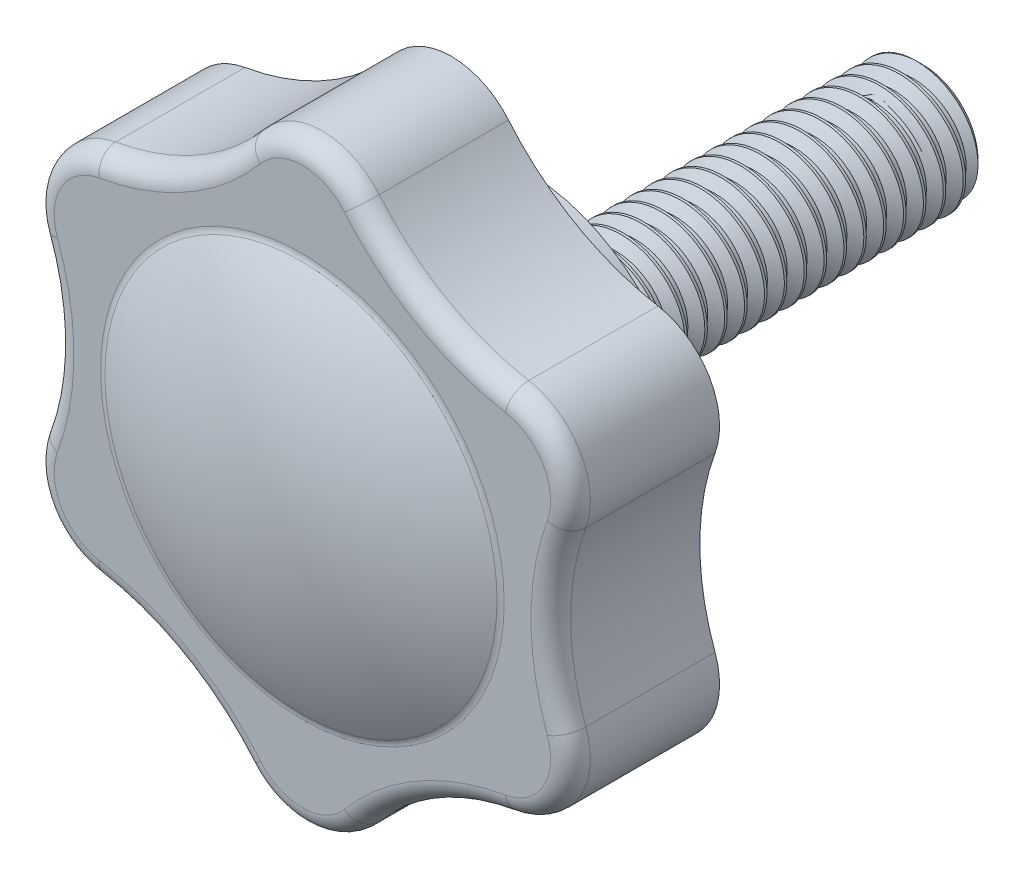
SolidWorks part; units mm, degrees
ref_plane "Front Plane" through (0, 0, 0) normal (0, 0, 1) x (1, 0, 0)
ref_plane "Top Plane" through (0, 0, 0) normal (0, 1, 0) x (1, 0, 0)
ref_plane "Right Plane" through (0, 0, 0) normal (1, 0, 0) x (0, 0, -1)
sketch "Sketch1" plane through (0, 0, 0) normal (0, 0, 1) x (1, 0, 0)
  circle A0 centre (0, 0) radius 6.5
  dimension "D1" = 13
extrude "Boss-Extrude1" add sketch "Sketch1" along normal blind 3
sketch "Sketch2" plane through (0, 0, 3) normal (0, 0, 1) x (1, 0, 0)
  line L0 (0, 0) -> (0, 17.4391) construction
  line L2 (14.0075, 8.0872) -> (0, 0) construction
  circle A0 centre (0, 0) radius 12 construction
  circle A1 centre (0, 0) radius 10 construction
  arc A2 (2.2988, 10.9276) -> (0, 12) centre (0, 9) ccw
  arc A3 (10.3923, 6) -> (8.3142, 7.4546) centre (7.7942, 4.5) ccw
  arc A4 (2.2988, 10.9276) -> (8.3142, 7.4546) centre (10.0727, 17.4464) ccw
  arc A5 (10.613, 3.473) -> (10.3923, 6) centre (7.7942, 4.5) ccw
  arc A6 (10.613, 3.473) -> (10.613, -3.473) centre (20.1453, 0) ccw
  arc A7 (10.3923, -6) -> (10.613, -3.473) centre (7.7942, -4.5) ccw
  arc A8 (8.3142, -7.4546) -> (10.3923, -6) centre (7.7942, -4.5) ccw
  arc A9 (8.3142, -7.4546) -> (2.2988, -10.9276) centre (10.0727, -17.4464) ccw
  arc A10 (0, -12) -> (2.2988, -10.9276) centre (0, -9) ccw
  arc A11 (-2.2988, -10.9276) -> (0, -12) centre (0, -9) ccw
  arc A12 (-2.2988, -10.9276) -> (-8.3142, -7.4546) centre (-10.0727, -17.4464) ccw
  arc A13 (-10.3923, -6) -> (-8.3142, -7.4546) centre (-7.7942, -4.5) ccw
  arc A14 (-10.613, -3.473) -> (-10.3923, -6) centre (-7.7942, -4.5) ccw
  arc A15 (-10.613, -3.473) -> (-10.613, 3.473) centre (-20.1453, 0) ccw
  arc A16 (-10.3923, 6) -> (-10.613, 3.473) centre (-7.7942, 4.5) ccw
  arc A17 (-8.3142, 7.4546) -> (-10.3923, 6) centre (-7.7942, 4.5) ccw
  arc A18 (-8.3142, 7.4546) -> (-2.2988, 10.9276) centre (-10.0727, 17.4464) ccw
  arc A19 (0, 12) -> (-2.2988, 10.9276) centre (0, 9) ccw
  dimension "D1" = 24
  dimension "D3" = 20
  dimension "D4" = 6
  dimension "D2" = 60
  dimension "D5" = 6
extrude "Boss-Extrude2" add sketch "Sketch2" along normal blind 6
sketch "Sketch4" plane through (0, 0, 0) normal (0, 1, 0) x (1, 0, 0)
  line L1 (6.5, 0) -> (-6.5, 0) construction
  line L2 (-8, -9) -> (8, -9) construction
  line L3 (-2.2988, -9) -> (2.2988, -9) construction
  line L4 (0, 0) -> (0, 4.0899) construction
  line L5 (-8, -9) -> (8, -9)
  line L6 (0, -11) -> (0, -9)
  arc A0 (-8, -9) -> (0, -11) centre (0, 6) ccw
  dimension "D1" = 11
  dimension "D2" = 16
revolve "Revolve3" add sketch "Sketch4" angle 360 about L4 region at (-3.025, 0, 9.8042)
sketch "Sketch6" plane through (0, 0, 3) normal (0, 0, -1) x (-1, 0, 0)
  circle A0 centre (0, 0) radius 8.5
  circle M2 centre (0, 0) radius 6.5
  dimension "D1" = 17
extrude "Cut-Extrude1" cut sketch "Sketch6" against normal blind 4 contours A0 M2 region at (8.2596, 0, 3)
fillet "Fillet1" radius 0.8 12 edges at (0, 12, 9) (5, 8.6603, 9) (10.3923, 6, 9) (10, 0, 9) (10.3923, -6, 9) (5, -8.6603, 9) (0, -12, 9) (-5, -8.6603, 9) (-10.3923, -6, 9) (-10, 0, 9) (-10.3923, 6, 9) (-5, 8.6603, 9)
fillet "Fillet2" radius 0.5 1 edges at (8, 0, 9)
sketch "Sketch7" plane through (0, 0, 0) normal (0, 0, -1) x (-1, 0, 0)
  circle A0 centre (0, 0) radius 2.5
  dimension "D1" = 5
extrude "Boss-Extrude3" add sketch "Sketch7" along normal blind 16
chamfer "Chamfer1" distance 0.3 angle 45 1 edges at (-2.5, 0, -16)
thread "Thread1" pitch 0.8 method cut profile "Thread Profile1" start angle 0, offset 1, length 0, pitch 0.8, diameter 5
ref_plane "Plane1" through (2.5, 0, -16.7) normal (0, -1, 0) x (1, 0, 0)
sketch "Thread Profile1" plane through (2.5, 0, -16.7) normal (0, -1, 0) x (1, 0, 0)
  line L0 (0, 0) -> (0, 0.8) construction
  line L11 (0, 0) -> (0, 0.7)
  line L12 (0, 0.7) -> (-0.433, 0.45)
  line L13 (-0.433, 0.45) -> (-0.433, 0.25)
  line L15 (-0.433, 0.25) -> (0, 0)
  line L17 (-0.433, 0.35) -> (0, 0.35) construction
  point P2 (0, 0)
  dimension "Pitch" = 0.8
  dimension "Profile_Angle" = 60
  dimension "Profile_Land" = 0.2
  dimension "Profile_Height" = 0.433
